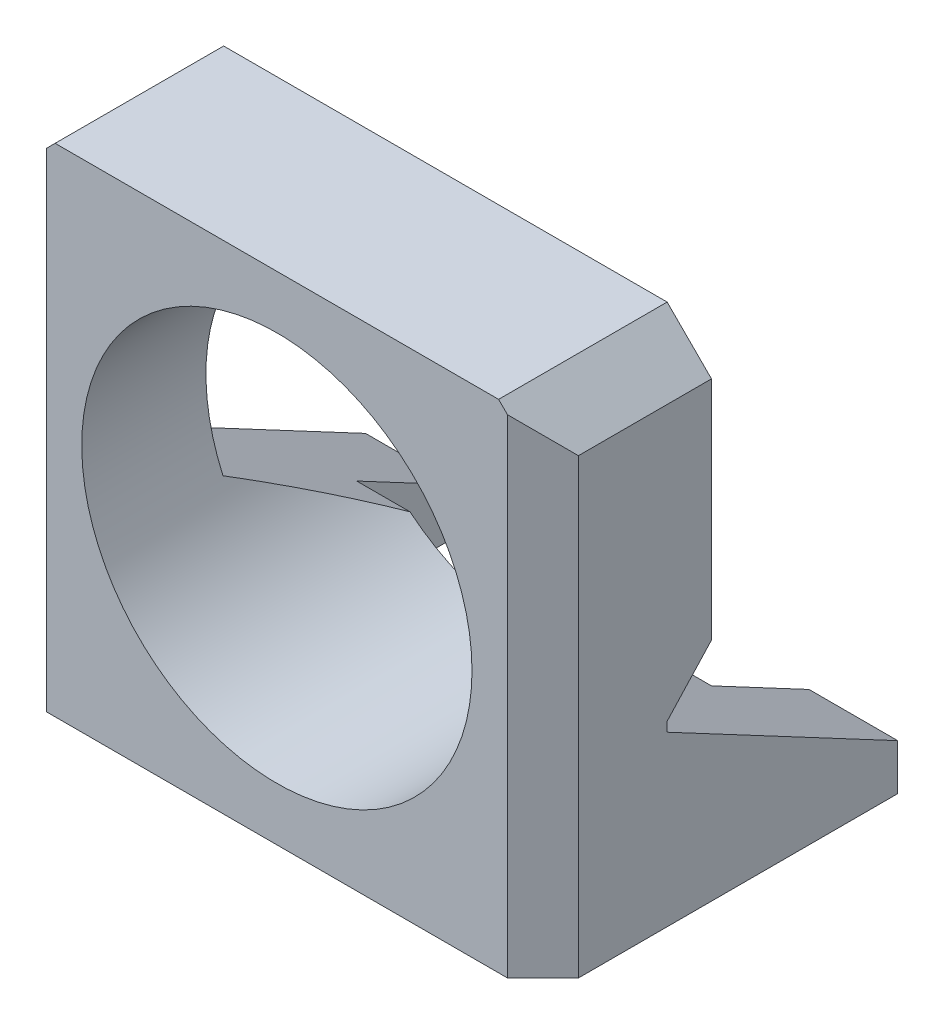
SolidWorks part; units mm, degrees
ref_plane "Front Plane" through (0, 0, 0) normal (0, 0, 1) x (1, 0, 0)
ref_plane "Top Plane" through (0, 0, 0) normal (0, 1, 0) x (1, 0, 0)
ref_plane "Right Plane" through (0, 0, 0) normal (1, 0, 0) x (0, 0, -1)
sketch "Sketch1" plane through (0, 0, 0) normal (0, 0, 1) x (1, 0, 0)
  line L0 (-15, 11.5) -> (-12.5, 14)
  line L1 (-12.5, 14) -> (12.5, 14)
  line L2 (-15, 11.5) -> (-15, -14)
  line L3 (-15, -14) -> (15, -14)
  line L4 (15, 11.5) -> (15, -14)
  line L5 (-15, 14) -> (15, -14) construction
  line L6 (-15, -14) -> (15, 14) construction
  line L7 (12.5, 14) -> (15, 11.5)
  circle A0 centre (0, 0) radius 11
  dimension "D1" = 22
  dimension "D2" = 30
  dimension "D3" = 28
extrude "Boss-Extrude1" add sketch "Sketch1" along normal blind 7
sketch "Sketch2" plane through (0, 0, 0) normal (0, 0, -1) x (-1, 0, 0)
  line L0 (0, 0) -> (0, -50000) construction
  line L1 (-15, -14) -> (-10, -14)
  line L2 (-15, -14) -> (-15, -11.5)
  line L3 (-15, -11.5) -> (-10, -11.5)
  line L4 (-10, -14) -> (-10, -11.5)
  line L5 (15, -11.5) -> (10, -11.5)
  line L6 (10, -14) -> (10, -11.5)
  line L7 (15, -14) -> (10, -14)
  line L8 (15, -14) -> (15, -11.5)
  dimension "D1" = 2.5
  dimension "D2" = 5
extrude "Boss-Extrude2" add sketch "Sketch2" along normal blind 13 contours L5 L6 L7 L8 | L2 L3 L4 L1
chamfer "Chamfer2" distance 2 angle 45 2 edges at (-10, -12.75, 0) (10, -12.75, 0)
sketch "Sketch5" plane through (0, -14, 0) normal (0, -1, 0) x (1, 0, 0)
  line L0 (-10, -7.5) -> (10, -7.5)
  line L1 (-10, -13) -> (-10, -2) construction
  line L2 (10, -13) -> (10, -2) construction
  line L3 (10, -7.5) -> (10, -2)
  line L4 (10, -2) -> (8, 0)
  line L5 (8, 0) -> (-8, 0)
  line L6 (-8, 0) -> (-10, -2)
  line L7 (-10, -2) -> (-10, -7.5)
  line M5 (-10, -13) -> (-10, -2)
  line M6 (-10, -2) -> (-8, 0)
  line M7 (-8, 0) -> (8, 0)
  line M8 (8, 0) -> (10, -2)
  line M9 (10, -2) -> (10, -13)
extrude "Boss-Extrude6" add sketch "Sketch5" against normal up to surface (2.5 mm away) contours L0 M5 M9 M8 M7 M6 region at (0, -14, -3.8345) up to face at (11.6, -11.5, -5.6)
chamfer "Chamfer3" distance 2 angle 45 1 edges at (15, -1.25, 7)
chamfer "Chamfer4" distance 2 angle 45 1 edges at (-15, -1.25, 7)
sketch "Sketch4" plane through (0, 0, 0) normal (0, 0, -1) x (-1, 0, 0)
  line L8 (0, 0) -> (0, 50000) construction
  line L14 (-15, -1.25) -> (15, 11.5)
  line L15 (15, 11.5) -> (12.5, 14)
  line L16 (12.5, 14) -> (-12.5, 14)
  line L17 (-12.5, 14) -> (-15, 11.5)
  line L18 (-15, 11.5) -> (-15, -1.25)
  line L19 (-15, 11.5) -> (-15, -14) construction
  point P8 (-15, -1.25)
extrude "Boss-Extrude4" add sketch "Sketch4" along normal blind 2.5
chamfer "Chamfer6" distance 2.5 2 edges at (12.9953, -0.398, 0) (-11.1504, 9.8639, 0)
chamfer "Chamfer7" distance 7 angle 62 1 edges at (0, -11.5, 0) first distance on face at (-0.5726, -4.3777, 0)
sketch "Sketch6" plane through (0, -14, 0) normal (0, -1, 0) x (1, 0, 0)
  line L0 (-15, 5) -> (-15, -13) construction
  line L1 (-8.3, 0.9412) -> (-8.3, 4.0588)
  line L2 (-8.3, 4.0588) -> (-11, 5.6177)
  line L3 (-11, 5.6177) -> (-13.7, 4.0588)
  line L4 (-13.7, 4.0588) -> (-13.7, 0.9412)
  line L5 (-13.7, 0.9412) -> (-11, -0.6177)
  line L6 (-11, -0.6177) -> (-8.3, 0.9412)
  line L7 (0, 0) -> (0, 50000) construction
  line L8 (11, -0.6177) -> (8.3, 0.9412)
  line L9 (13.7, 0.9412) -> (11, -0.6177)
  line L10 (13.7, 4.0588) -> (13.7, 0.9412)
  line L11 (11, 5.6177) -> (13.7, 4.0588)
  line L12 (8.3, 4.0588) -> (11, 5.6177)
  line L13 (8.3, 0.9412) -> (8.3, 4.0588)
  circle A0 centre (-11, 2.5) radius 1.5 construction
  circle A1 centre (-11, 2.5) radius 1.5
  circle A2 centre (-11, 2.5) radius 2.7 construction
  dimension "D1" = 5.4
extrude "Cut-Extrude1" cut sketch "Sketch6" against normal blind 2.5 from offset 3 offset against normal yes
sketch "Sketch7" plane through (0, -14, 0) normal (0, -1, 0) x (1, 0, 0)
  circle A0 centre (11, 2.5) radius 1.5 construction
  circle A1 centre (-11, 2.5) radius 1.5 construction
  circle A2 centre (11, 2.5) radius 1.5
  circle A3 centre (-11, 2.5) radius 1.5
extrude "Cut-Extrude2" cut sketch "Sketch7" against normal blind 6
